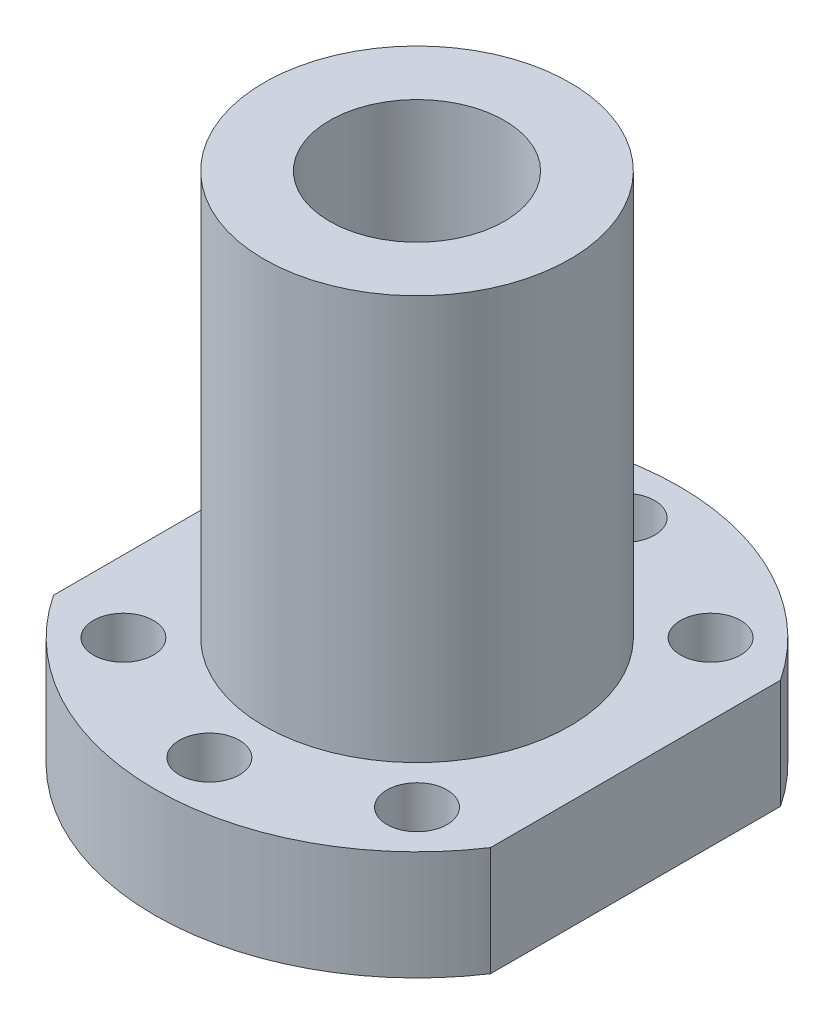
SolidWorks part; units mm, degrees
material "不锈钢 (铁素体)"
ref_plane "前视基准面" through (0, 0, 0) normal (0, 0, 1) x (1, 0, 0)
ref_plane "上视基准面" through (0, 0, 0) normal (0, 1, 0) x (1, 0, 0)
ref_plane "右视基准面" through (0, 0, 0) normal (1, 0, 0) x (0, 0, -1)
sketch "草图1" plane through (0, 0, 0) normal (0, 1, 0) x (1, 0, 0)
  line L0 (0, 31.2311) -> (0, -30.3147) construction
  line L1 (-42.0581, 0) -> (42.8284, 0) construction
  line L2 (-20, 13.2665) -> (-20, -13.2665)
  line L3 (20, 13.2665) -> (20, -13.2665)
  circle A0 centre (0, 0) radius 8
  circle A1 centre (0, 0) radius 14
  arc A2 (-20, -13.2665) -> (20, -13.2665) centre (0, 0) ccw
  circle A3 centre (0, 0) radius 19 construction
  arc A4 (20, 13.2665) -> (-20, 13.2665) centre (0, 0) ccw
  circle A5 centre (0, -19) radius 2.75
  circle A6 centre (-13.435, -13.435) radius 2.75
  circle A7 centre (13.435, -13.435) radius 2.75
  circle A8 centre (13.435, 13.435) radius 2.75
  circle A9 centre (0, 19) radius 2.75
  circle A10 centre (-13.435, 13.435) radius 2.75
  dimension "D1" = 16
  dimension "D2" = 28
  dimension "D3" = 48
  dimension "D4" = 38
  dimension "D6" = 5.5
  dimension "D5" = 40
  dimension "D7" = 90
extrude "凸台-拉伸1" add sketch "草图1" along normal blind 10 contours L3 A4 L2 A2 A9 A8 A1 A5 A6 A7 A10 region at (0, 0, -23.3752)
extrude "凸台-拉伸2" add sketch "草图1<3>" along normal blind 47 contours A1 A0 region at (-13.604, 0, 0)
sketch "草图1<3>" plane through (0, 0, 0) normal (0, 1, 0) x (1, 0, 0) same geometry as "草图1"
sketch "草图2" plane through (-20, 0, 0) normal (-1, 0, 0) x (0, 0, 1)
  line L0 (0, 0) -> (0, 10) construction
  line L1 (-13.2665, 10) -> (13.2665, 10) construction
  line L3 (-13.2665, 10) -> (-13.2665, 0) construction
  line L4 (-13.2665, 5) -> (13.2665, 5) construction
  line L5 (13.2665, 10) -> (13.2665, 0) construction
  circle A0 centre (0, 5) radius 3
  dimension "D1" = 6
extrude "切除-拉伸1" cut sketch "草图2" against normal blind 20
